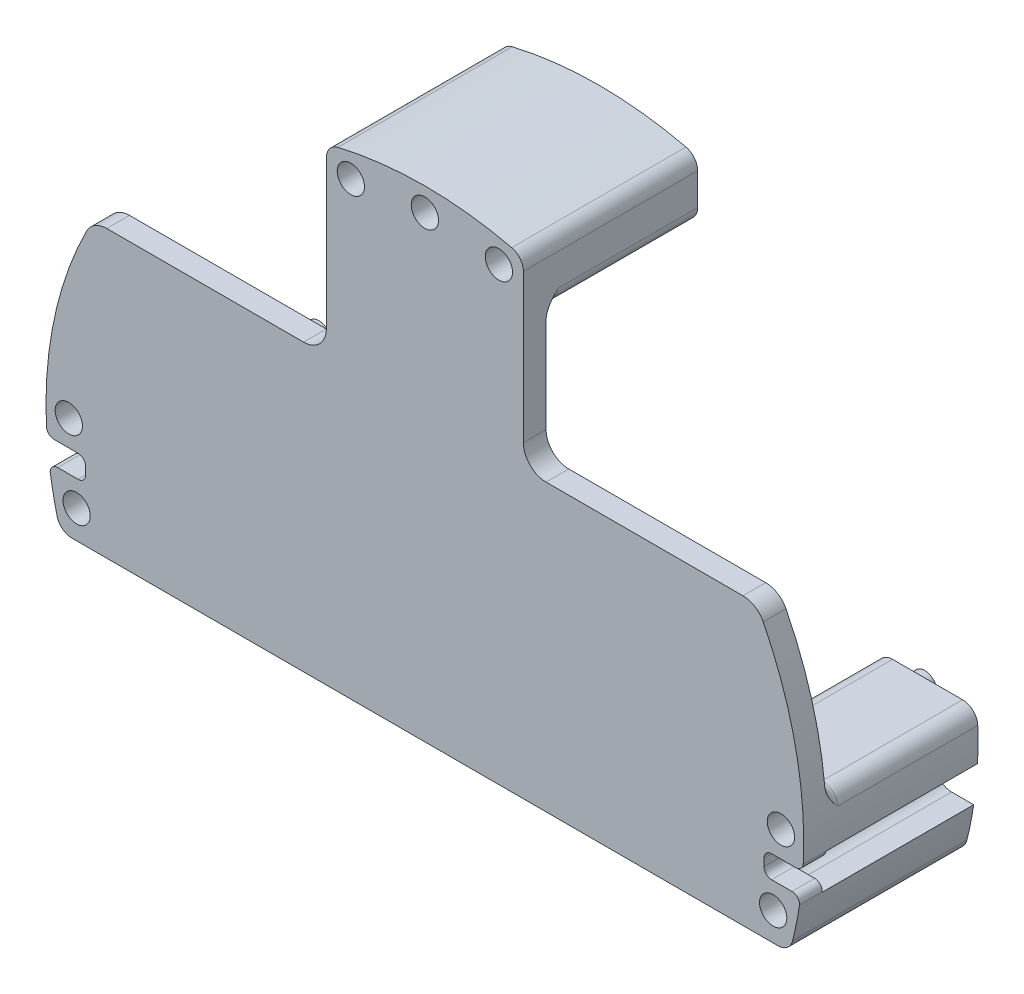
SolidWorks part; units mm, degrees
ref_plane "Front Plane" through (0, 0, 0) normal (0, 0, 1) x (1, 0, 0)
ref_plane "Top Plane" through (0, 0, 0) normal (0, 1, 0) x (1, 0, 0)
ref_plane "Right Plane" through (0, 0, 0) normal (1, 0, 0) x (0, 0, -1)
sketch "Sketch1" plane through (0, 0, 0) normal (0, 0, 1) x (1, 0, 0)
  circle A0 centre (0, 0) radius 50
  dimension "D1" = 100
extrude "Boss-Extrude1" add sketch "Sketch1" along normal blind 3
sketch "Sketch2" plane through (0, 0, 0) normal (0, 0, -1) x (-1, 0, 0)
  line L0 (14, 46.4247) -> (14, 38.9389) construction
  line L1 (-14, 38.9389) -> (-14, 46.4247) construction
  line L2 (14, 46.4247) -> (14, 38.9389) construction
  line L3 (-14, 38.9389) -> (-14, 46.4247) construction
  line L4 (20.4188, -14.0511) -> (-46.4758, -14.0511) construction
  line L5 (-42.0264, 25.1389) -> (-38.74, 25.1389) construction
  line L6 (20.4188, -14.0511) -> (-46.4758, -14.0511) construction
  line L7 (-42.0264, 25.1389) -> (-38.74, 25.1389) construction
  line L8 (38.74, 25.1389) -> (42.0265, 25.1389) construction
  line L9 (38.74, 25.1389) -> (42.0265, 25.1389) construction
  line L10 (-48.4426, -6.4208) -> (-45.7608, -6.4208) construction
  line L11 (-44.7608, -5.4208) -> (-44.7608, -4.4511) construction
  line L12 (-45.7608, -3.4511) -> (-48.9412, -3.4511) construction
  line L13 (-48.4426, -6.4208) -> (-45.7608, -6.4208)
  line L14 (-44.7608, -5.4208) -> (-44.7608, -4.4511)
  line L15 (-45.7608, -3.4511) -> (-48.9412, -3.4511)
  line L16 (45.7608, -6.4209) -> (48.4426, -6.4209) construction
  line L17 (44.7608, -4.4511) -> (44.7608, -5.4209) construction
  line L18 (48.9412, -3.4511) -> (45.7608, -3.4511) construction
  line L19 (45.7608, -6.4209) -> (48.4426, -6.4209)
  line L20 (44.7608, -4.4511) -> (44.7608, -5.4209)
  line L21 (48.9412, -3.4511) -> (45.7608, -3.4511)
  line L22 (-0.427, 43.2631) -> (13.0731, 43.2631) construction
  line L23 (-0.427, 43.2631) -> (13.0731, 43.2631) construction
  line L24 (-40.3963, 19.635) -> (-38.66, 21.3713) construction
  line L25 (-40.3963, 19.635) -> (-38.66, 21.3713) construction
  line L26 (-42.2208, 13.254) -> (-42.2208, -1.623) construction
  line L27 (-42.2208, 13.254) -> (-42.2208, -1.623) construction
  line L28 (-42.2209, -12.873) -> (-42.2209, 0.627) construction
  line L29 (-42.2209, -12.873) -> (-42.2209, 0.627) construction
  line L30 (38.279, 20.9903) -> (40.0153, 19.254) construction
  line L31 (42.3521, 0.627) -> (42.3521, -12.873) construction
  line L32 (42.3521, -1.623) -> (42.3521, 13.254) construction
  line L33 (38.279, 20.9903) -> (40.0153, 19.254) construction
  line L34 (42.3521, 0.627) -> (42.3521, -12.873) construction
  line L35 (42.3521, -1.623) -> (42.3521, 13.254) construction
  circle A0 centre (45.9632, -9.8209) radius 1.8 construction
  circle A1 centre (46.9901, -0.0511) radius 1.8 construction
  circle A2 centre (45.9632, 9.7188) radius 1.8 construction
  circle A3 centre (9.7699, 45.9121) radius 1.8 construction
  circle A4 centre (0, 46.939) radius 1.8 construction
  circle A5 centre (-9.7699, 45.9121) radius 1.8 construction
  circle A6 centre (-45.9632, -9.8209) radius 1.8 construction
  circle A7 centre (-46.9901, -0.0511) radius 1.8 construction
  circle A8 centre (-45.9632, 9.7188) radius 1.8 construction
  circle A9 centre (45.9632, -9.8209) radius 1.8
  circle A10 centre (46.9901, -0.0511) radius 1.8
  circle A11 centre (45.9632, 9.7188) radius 1.8
  circle A12 centre (9.7699, 45.9121) radius 1.8
  circle A13 centre (0, 46.939) radius 1.8
  circle A14 centre (-9.7699, 45.9121) radius 1.8
  circle A15 centre (-45.9632, -9.8209) radius 1.8
  circle A16 centre (-46.9901, -0.0511) radius 1.8
  circle A17 centre (-45.9632, 9.7188) radius 1.8
  arc A18 (-49.94, -2.5) -> (-48.9412, -3.4511) centre (-48.9412, -2.4511) ccw construction
  arc A19 (-48.4426, -6.4208) -> (-49.4312, -7.5712) centre (-48.4426, -7.4208) ccw construction
  arc A20 (-45.7608, -6.4208) -> (-44.7608, -5.4208) centre (-45.7608, -5.4208) ccw construction
  arc A21 (-44.7608, -4.4511) -> (-45.7608, -3.4511) centre (-45.7608, -4.4511) ccw construction
  arc A22 (-49.94, -2.5) -> (-48.9412, -3.4511) centre (-48.9412, -2.4511) ccw
  arc A23 (-48.4426, -6.4208) -> (-49.4312, -7.5712) centre (-48.4426, -7.4208) ccw
  arc A24 (-45.7608, -6.4208) -> (-44.7608, -5.4208) centre (-45.7608, -5.4208) ccw
  arc A25 (-44.7608, -4.4511) -> (-45.7608, -3.4511) centre (-45.7608, -4.4511) ccw
  arc A26 (44.7608, -5.4209) -> (45.7608, -6.4209) centre (45.7608, -5.4209) ccw construction
  arc A27 (45.7608, -3.4511) -> (44.7608, -4.4511) centre (45.7608, -4.4511) ccw construction
  arc A28 (48.9412, -3.4511) -> (49.94, -2.5001) centre (48.9412, -2.4511) ccw construction
  arc A29 (49.4312, -7.5713) -> (48.4426, -6.4209) centre (48.4426, -7.4209) ccw construction
  arc A30 (44.7608, -5.4209) -> (45.7608, -6.4209) centre (45.7608, -5.4209) ccw
  arc A31 (45.7608, -3.4511) -> (44.7608, -4.4511) centre (45.7608, -4.4511) ccw
  arc A32 (48.9412, -3.4511) -> (49.94, -2.5001) centre (48.9412, -2.4511) ccw
  arc A33 (49.4312, -7.5713) -> (48.4426, -6.4209) centre (48.4426, -7.4209) ccw
  arc A34 (-49.94, -2.5) -> (-49.4312, -7.5712) centre (-44.6835, -4.5338) ccw
  arc A35 (49.94, -2.5001) -> (49.4312, -7.5713) centre (49.0397, -4.9709) cw
  circle A36 centre (38.3005, -27.2416) radius 1.8 construction
  circle A37 centre (44.1819, 15.9698) radius 1.2 construction
  circle A38 centre (41.555, 21.9154) radius 1.2 construction
  circle A39 centre (32.7399, 26.939) radius 1.8 construction
  circle A40 centre (4.9119, 46.6815) radius 1.2 construction
  circle A41 centre (-4.9119, 46.6815) radius 1.2 construction
  circle A42 centre (-32.7399, 26.939) radius 1.8 construction
  circle A43 centre (-41.555, 21.9154) radius 1.2 construction
  circle A44 centre (-44.1819, 15.9698) radius 1.2 construction
  circle A45 centre (38.3005, -27.2416) radius 1.8 construction
  circle A46 centre (44.1819, 15.9698) radius 1.2 construction
  circle A47 centre (41.555, 21.9154) radius 1.2 construction
  circle A48 centre (32.7399, 26.939) radius 1.8 construction
  circle A49 centre (4.9119, 46.6815) radius 1.2 construction
  circle A50 centre (-4.9119, 46.6815) radius 1.2 construction
  circle A51 centre (-32.7399, 26.939) radius 1.8 construction
  circle A52 centre (-41.555, 21.9154) radius 1.2 construction
  circle A53 centre (-44.1819, 15.9698) radius 1.2 construction
extrude "Cut-Extrude1" cut sketch "Sketch2" against normal through all
sketch "Sketch3" plane through (0, 0, 0) normal (0, 0, -1) x (-1, 0, 0)
  line L0 (-48.1287, -13.5511) -> (-42.7209, -13.5511)
  line L1 (-42.7209, -13.5511) -> (-42.7209, 14.254)
  line L2 (-42.7209, 14.254) -> (-47.9252, 14.254) construction
  line L9 (20.4188, -14.0511) -> (-46.4758, -14.0511) construction
  line L10 (-42.2209, -12.873) -> (-42.2209, 0.627) construction
  line L11 (0, 0) -> (0, 49.9989) construction
  line L12 (0, 43.5131) -> (-13, 43.5131)
  line L13 (-13, 43.5131) -> (-13, 48.2804)
  line L14 (-14, 38.9389) -> (-14, 46.4247) construction
  line L15 (-0.427, 43.2631) -> (13.0731, 43.2631) construction
  line L16 (0, 43.5131) -> (13, 43.5131)
  line L17 (13, 43.5131) -> (13, 48.2804)
  line L24 (-42.7209, 14.254) -> (-40.8963, 19.635)
  line L25 (-40.8963, 19.635) -> (-36.3924, 24.1389)
  line L26 (-36.3924, 24.1389) -> (-43.7871, 24.1389)
  line L27 (-40.3963, 19.635) -> (-40.8963, 19.635) construction
  line L28 (-40.3963, 19.635) -> (-40.3963, 14.254) construction
  line L29 (-40.3963, 14.254) -> (-42.7209, 14.254) construction
  line L30 (-40.3963, 19.635) -> (-38.66, 21.3713) construction
  line L31 (-42.0264, 25.1389) -> (-38.74, 25.1389) construction
  line L32 (-49.4311, -7.5208) -> (-44.5108, -7.5208)
  line L33 (-48.4426, -6.4208) -> (-45.7608, -6.4208) construction
  line L34 (40.3963, 14.254) -> (42.7209, 14.254) construction
  line L35 (40.3963, 19.635) -> (40.3963, 14.254) construction
  line L44 (-49.9338, -2.5725) -> (-44.5108, -2.5725)
  line L45 (-44.5108, -2.5725) -> (-44.5108, -7.5208)
  line L50 (-44.7608, -5.4208) -> (-44.7608, -4.4511) construction
  line L69 (40.3963, 19.635) -> (40.8963, 19.635) construction
  line L70 (42.7209, 14.254) -> (47.9252, 14.254) construction
  line L71 (44.5108, -2.5725) -> (44.5108, -7.5208)
  line L72 (49.9338, -2.5725) -> (44.5108, -2.5725)
  line L73 (49.4311, -7.5208) -> (44.5108, -7.5208)
  line L74 (36.3924, 24.1389) -> (43.7871, 24.1389)
  line L75 (40.8963, 19.635) -> (36.3924, 24.1389)
  line L76 (42.7209, 14.254) -> (40.8963, 19.635)
  line L77 (42.7209, -13.5511) -> (42.7209, 14.254)
  line L78 (48.1287, -13.5511) -> (42.7209, -13.5511)
  arc A0 (-49.4423, -7.4473) -> (49.4423, -7.4473) centre (0, 0) ccw construction
  arc A1 (49.9338, -2.5729) -> (-49.9338, -2.5725) centre (0, 0) ccw construction
  arc A2 (-47.9252, 14.254) -> (-49.9338, -2.5725) centre (0, 0) ccw
  arc A12 (-13, 48.2804) -> (13, 48.2804) centre (0, 0) cw
  circle A19 centre (-45.9632, 9.7188) radius 1.8 construction
  circle A20 centre (-46.9901, -0.0511) radius 1.8 construction
  circle A21 centre (-45.9632, -9.8209) radius 1.8 construction
  circle A22 centre (-9.7699, 45.9121) radius 1.8 construction
  circle A26 centre (9.7699, 45.9121) radius 1.8 construction
  circle A27 centre (0, 46.939) radius 1.8 construction
  circle A31 centre (9.7699, 45.9121) radius 1.8
  circle A32 centre (0, 46.939) radius 1.8
  circle A33 centre (-9.7699, 45.9121) radius 1.8
  circle A34 centre (-45.9632, -9.8209) radius 1.8
  circle A35 centre (-46.9901, -0.0511) radius 1.8
  circle A36 centre (-45.9632, 9.7188) radius 1.8 construction
  arc A37 (-43.7871, 24.1389) -> (-47.9252, 14.254) centre (0, 0) ccw
  arc A58 (-48.1287, -13.5511) -> (-49.4311, -7.5208) centre (0, 0) cw
  circle A59 centre (45.9632, 9.7188) radius 1.8 construction
  arc A60 (48.1287, -13.5511) -> (49.4311, -7.5208) centre (0, 0) ccw
  arc A61 (43.7871, 24.1389) -> (47.9252, 14.254) centre (0, 0) cw
  circle A62 centre (46.9901, -0.0511) radius 1.8
  circle A63 centre (45.9632, -9.8209) radius 1.8
  arc A64 (47.9252, 14.254) -> (49.9338, -2.5725) centre (0, 0) cw
  dimension "D1" = 0.5
  dimension "D2" = 0.5
  dimension "D3" = 1
  dimension "D4" = 1
  dimension "D5" = 0.25
  dimension "D6" = 0.5
  dimension "D7" = 1
  dimension "D8" = 0.25
  dimension "D9" = 1.1
extrude "Boss-Extrude2" add sketch "Sketch3" along normal blind 20
sketch "Sketch10" plane through (0, 0, -20) normal (0, 0, -1) x (-1, 0, 0)
  line L3 (0, 0) -> (0, 43.5131) construction
  line L8 (-42.7209, -13.5511) -> (-42.7209, 14.254) construction
  line L10 (-42.7209, -13.5511) -> (-42.7209, 3.7489)
  line L16 (-36.7209, 3.7489) -> (-36.7209, -13.5511)
  line L17 (-36.7209, -13.5511) -> (-42.7209, -13.5511)
  line L18 (-13, 43.5131) -> (13, 43.5131) construction
  line L19 (42.7209, 3.7489) -> (36.7209, 3.7489)
  line L26 (-42.7209, 3.7489) -> (-36.7209, 3.7489)
  line L27 (-42.7209, 3.7489) -> (-49.8593, 3.7489) construction
  line L28 (-46.9901, 1.7489) -> (-42.7209, 1.7489) construction
  line L29 (42.7209, -13.5511) -> (42.7209, 3.7489)
  line L30 (36.7209, -13.5511) -> (42.7209, -13.5511)
  line L31 (36.7209, 3.7489) -> (36.7209, -13.5511)
  arc A0 (-43.7871, 24.1389) -> (-49.9338, -2.5725) centre (0, 0) ccw construction
  circle A1 centre (-46.9901, -0.0511) radius 1.8 construction
  dimension "D1" = 6
  dimension "D2" = 2
extrude "Boss-Extrude6" add sketch "Sketch10" against normal up to surface (20 mm away) up to face at (0, 16.4713, 0)
sketch "Sketch4" plane through (0, 0, -20) normal (0, 0, -1) x (-1, 0, 0)
  circle A0 centre (41.555, 21.9154) radius 1.2 construction
  circle A1 centre (44.1819, 15.9698) radius 1.2 construction
  circle A2 centre (-44.1819, 15.9698) radius 1.2 construction
  circle A3 centre (-41.555, 21.9154) radius 1.2 construction
  circle A4 centre (41.555, 21.9154) radius 1.2 construction
  circle A5 centre (44.1819, 15.9698) radius 1.2 construction
  circle A6 centre (-44.1819, 15.9698) radius 1.2 construction
  circle A7 centre (-41.555, 21.9154) radius 1.2 construction
  circle A8 centre (-41.555, 21.9154) radius 1.1
  circle A9 centre (-44.1819, 15.9698) radius 1.1
  circle A10 centre (41.555, 21.9154) radius 1.1
  circle A11 centre (44.1819, 15.9698) radius 1.1
  circle A12 centre (45.9632, 9.7188) radius 1.8 construction
  circle A13 centre (-45.9632, 9.7188) radius 1.8 construction
  circle A14 centre (45.9632, 9.7188) radius 1.8 construction
  circle A15 centre (-45.9632, 9.7188) radius 1.8 construction
  circle A16 centre (-45.9632, 9.7188) radius 1.6
  circle A17 centre (45.9632, 9.7188) radius 1.6
  circle A18 centre (4.9119, 46.6815) radius 1.2 construction
  circle A19 centre (-4.9119, 46.6815) radius 1.2 construction
  circle A20 centre (4.9119, 46.6815) radius 1.2 construction
  circle A21 centre (-4.9119, 46.6815) radius 1.2 construction
  circle A22 centre (-4.9119, 46.6815) radius 1.1
  circle A23 centre (4.9119, 46.6815) radius 1.1
  dimension "D1" = 2.2
  dimension "D2" = 3.2
extrude "Boss-Extrude3" add sketch "Sketch4" along normal blind 1.6
sketch "Sketch14" plane through (0, 0, 0) normal (0, 0, -1) x (-1, 0, 0)
  line L0 (13, 43.5131) -> (13, 48.2804) construction
  line L1 (-13, 43.5131) -> (13, 43.5131)
  line L2 (-13, 43.5131) -> (-13, 40.5131)
  line L3 (-13, 40.5131) -> (13, 40.5131)
  line L4 (13, 43.5131) -> (13, 40.5131)
  dimension "D1" = 3
extrude "Boss-Extrude8" add sketch "Sketch14" along normal up to surface (20 mm away) up to face at (-3.8119, 46.6815, -20)
sketch "Sketch11" plane through (0, 0, -20) normal (0, 0, -1) x (-1, 0, 0)
  line L0 (-45.9632, 9.7188) -> (45.9632, 9.7188) construction
  line L1 (45.9632, 9.7188) -> (44.1819, 15.9698) construction
  line L2 (44.1819, 15.9698) -> (-44.1822, 15.9698) construction
  line L3 (-44.1822, 15.9698) -> (-41.555, 21.9154) construction
  line L4 (-41.555, 21.9154) -> (41.555, 21.9154) construction
  line L5 (-45.9632, -9.8209) -> (45.9632, -9.8209) construction
  line L6 (45.9632, -9.8209) -> (-46.9798, 0) construction
  line L7 (-46.9798, 0) -> (46.9798, 0) construction
  circle A0 centre (0, 0) radius 39.9798 construction
  circle A1 centre (0, 0) radius 46.9798 construction
  circle A11 centre (-39.9798, 0) radius 1.6
  circle A12 centre (-38.7548, -9.8209) radius 1.6
  circle A13 centre (38.7548, -9.8209) radius 1.6
  circle A14 centre (39.9798, 0) radius 1.6
  circle A15 centre (-45.9632, 9.7188) radius 1.6 construction
  dimension "D1" = 7
extrude "Boss-Extrude7" add sketch "Sketch11" along normal blind 3
sketch "Sketch15" plane through (0, 0, -20) normal (0, 0, -1) x (-1, 0, 0)
  line L0 (-13, 41.7631) -> (13, 41.7631) construction
  line L1 (-13, 48.2804) -> (-13, 40.5131) construction
  line L2 (13, 40.5131) -> (13, 48.2804) construction
  line L3 (13, 41.7631) -> (4.9119, 46.6815) construction
  line L4 (4.9119, 46.6815) -> (-4.9119, 46.6815) construction
  line L5 (-4.9119, 46.6815) -> (-4.9119, 40.5131) construction
  line L6 (-13, 40.5131) -> (13, 40.5131) construction
  line L7 (-4.9119, 40.5131) -> (4.9119, 46.6815) construction
  line L8 (4.9119, 46.6815) -> (4.9119, 40.5131) construction
  line L9 (13, 40.5131) -> (-13, 40.5131) construction
  circle A0 centre (-4.9119, 41.7631) radius 1.1
  circle A1 centre (4.9119, 41.7631) radius 1.1
  circle A2 centre (-4.9119, 46.6815) radius 1.1 construction
  circle A3 centre (4.9119, 46.6815) radius 1.1 construction
  dimension "D1" = 1.25
extrude "Boss-Extrude9" add sketch "Sketch15" along normal up to surface (3 mm away) up to face at (38.3798, 0, -23)
sketch "Sketch13" plane through (0, 0, -21.6) normal (0, 0, -1) x (-1, 0, 0)
  circle A0 centre (45.9632, 9.7188) radius 1.6 construction
  circle A1 centre (44.1819, 15.9698) radius 1.1 construction
  circle A2 centre (41.555, 21.9154) radius 1.1 construction
  circle A3 centre (-41.555, 21.9154) radius 1.1 construction
  circle A4 centre (-44.1819, 15.9698) radius 1.1 construction
  circle A5 centre (-45.9632, 9.7188) radius 1.6 construction
  circle A6 centre (45.9632, 9.7188) radius 1.6
  circle A7 centre (44.1819, 15.9698) radius 1.1
  circle A8 centre (41.555, 21.9154) radius 1.1
  circle A9 centre (-41.555, 21.9154) radius 1.1
  circle A10 centre (-44.1819, 15.9698) radius 1.1
  circle A11 centre (-45.9632, 9.7188) radius 1.6
  circle A12 centre (4.9119, 46.6815) radius 1.1 construction
  circle A13 centre (-4.9119, 46.6815) radius 1.1 construction
  circle A14 centre (4.9119, 46.6815) radius 1.1
  circle A15 centre (-4.9119, 46.6815) radius 1.1
extrude "Cut-Extrude6" cut sketch "Sketch13" against normal up to surface (1.6 mm away) up to face at (40.3548, -9.8209, -20)
sketch "Sketch16" plane through (0, 0, -20) normal (0, 0, -1) x (-1, 0, 0)
  line L0 (-42.7209, 3.7489) -> (-49.8593, 3.7489)
  line L1 (-36.3924, 24.1389) -> (-43.7871, 24.1389) construction
  line L2 (-40.8963, 19.635) -> (-36.3924, 24.1389) construction
  line L3 (-42.7209, 14.254) -> (-40.8963, 19.635) construction
  line L4 (-42.7209, 3.7489) -> (-42.7209, 14.254) construction
  line L5 (-36.3924, 24.1389) -> (-43.7871, 24.1389)
  line L6 (-40.8963, 19.635) -> (-36.3924, 24.1389)
  line L7 (-42.7209, 14.254) -> (-40.8963, 19.635)
  line L8 (-42.7209, 3.7489) -> (-42.7209, 14.254)
  line L9 (0, 0) -> (0, 40.5131) construction
  line L10 (-13, 40.5131) -> (13, 40.5131) construction
  line L11 (40.8963, 19.635) -> (36.3924, 24.1389)
  line L12 (42.7209, 14.254) -> (40.8963, 19.635)
  line L13 (42.7209, 3.7489) -> (42.7209, 14.254)
  line L14 (42.7209, 3.7489) -> (49.8593, 3.7489)
  line L15 (36.3924, 24.1389) -> (43.7871, 24.1389)
  arc A0 (-43.7871, 24.1389) -> (-49.9338, -2.5725) centre (0, 0) ccw construction
  arc A1 (-43.7871, 24.1389) -> (-49.8593, 3.7489) centre (0, 0) ccw
  arc A2 (43.7871, 24.1389) -> (49.8593, 3.7489) centre (0, 0) cw
extrude "Cut-Extrude7" cut sketch "Sketch16" against normal up to surface (20 mm away) up to face at (0, 13.6268, 0)
sketch "Sketch17" plane through (0, 0, 0) normal (0, 0, -1) x (-1, 0, 0)
  line L0 (-48.1287, -13.5511) -> (48.1287, -13.5511)
  arc A0 (-48.1287, -13.5511) -> (48.1287, -13.5511) centre (0, 0) ccw construction
  arc A1 (-48.1287, -13.5511) -> (48.1287, -13.5511) centre (0, 0) ccw
extrude "Cut-Extrude8" cut sketch "Sketch17" against normal through all both and the other way through all
fillet "Fillet1" radius 2 16 edges at (-36.7209, 3.7489, -10) (-36.7209, -13.5511, -10) (36.7209, -13.5511, -10) (36.7209, 3.7489, -10) (-13, 48.2804, -10) (44.5108, -7.5208, -10) (44.5108, -2.5725, -10) (-44.5108, -7.5208, -10) (-44.5108, -2.5725, -10) (-49.8593, 3.7489, -10) (-48.1287, -13.5511, -8.5) (-13, 40.5131, -10) (13, 48.2804, -10) (13, 40.5131, -10) (49.8593, 3.7489, -10) (48.1287, -13.5511, -8.5)
sketch "Sketch18" plane through (0, 0, 0) normal (0, 0, -1) x (-1, 0, 0)
  line L0 (-40.8905, 27.1389) -> (-33, 27.1389) construction
  line L1 (-13, 29.1389) -> (-13, 46.7226) construction
  line L2 (-40.8905, 27.1389) -> (-15, 27.1389)
  line L3 (-13, 29.1389) -> (-13, 46.7226)
  line L4 (0, 0) -> (0, 47.7712) construction
  line L5 (13, 29.1389) -> (13, 46.7226)
  line L6 (40.8905, 27.1389) -> (15, 27.1389)
  arc A0 (-40.8905, 27.1389) -> (-42.5943, 26.1864) centre (-40.8905, 25.1389) ccw construction
  arc A2 (-11.4583, 48.6694) -> (-13, 46.7226) centre (-11, 46.7226) ccw construction
  arc A3 (-40.8905, 27.1389) -> (-42.5943, 26.1864) centre (-40.8905, 25.1389) ccw
  arc A4 (-15, 27.1389) -> (-13, 29.1389) centre (-15, 29.1389) ccw
  arc A5 (-11.4583, 48.6694) -> (-13, 46.7226) centre (-11, 46.7226) ccw
  arc A6 (-11.4583, 48.6694) -> (-42.5943, 26.1864) centre (0, 0) ccw
  arc A7 (11.4583, 48.6694) -> (13, 46.7226) centre (11, 46.7226) cw
  arc A8 (15, 27.1389) -> (13, 29.1389) centre (15, 29.1389) cw
  arc A9 (40.8905, 27.1389) -> (42.5943, 26.1864) centre (40.8905, 25.1389) cw
  arc A10 (11.4583, 48.6694) -> (42.5943, 26.1864) centre (0, 0) cw
  dimension "D1" = 2
extrude "Cut-Extrude9" cut sketch "Sketch18" against normal through all both
fillet "Fillet2" radius 1.5 13 edges at (12.4142, 41.0989, 0) (-12.4142, 41.0989, 0) (-49.3563, 3.1887, 0) (-43.3445, 3.7489, 0) (-37.3067, 3.1632, 0) (-37.3067, -12.9653, 0) (37.3067, -12.9653, 0) (49.3563, 3.1887, 0) (43.3445, 3.7489, 0) (37.3067, 3.1632, 0) (0, 40.5131, 0) (-36.7209, -4.9011, 0) (36.7209, -4.9011, 0)
sketch "Sketch9" plane through (0, 0, 3) normal (0, 0, 1) x (1, 0, 0)
  circle A0 centre (45.9632, 9.7188) radius 1.8 construction
  circle A2 centre (45.9632, 9.7188) radius 1.8
  circle A4 centre (-45.9632, 9.7188) radius 1.8 construction
  circle A5 centre (-45.9632, 9.7188) radius 1.8
extrude "Boss-Extrude5" add sketch "Sketch9" against normal up to surface (3 mm away) up to face at (0, 15.0845, 0)
sketch "Sketch24" plane through (0, 0, 0) normal (0, 0, -1) x (-1, 0, 0)
  line L0 (0, 40.5131) -> (0, 0) construction
  line L1 (-13, 29.1389) -> (-53, 29.1389)
  line L2 (-13, 29.1389) -> (-13, 24.1389)
  line L3 (-13, 24.1389) -> (-53, 24.1389)
  line L4 (-53, 29.1389) -> (-53, 24.1389)
  line L5 (11, 40.5131) -> (-11, 40.5131) construction
  line L6 (13, 24.1389) -> (53, 24.1389)
  line L7 (53, 29.1389) -> (53, 24.1389)
  line L8 (13, 29.1389) -> (53, 29.1389)
  line L9 (13, 29.1389) -> (13, 24.1389)
  line L10 (-13, 29.1389) -> (-13, 39.6408) construction
  arc A0 (-15, 27.1389) -> (-13, 29.1389) centre (-15, 29.1389) ccw construction
  dimension "D1" = 40
  dimension "D2" = 5
extrude "Cut-Extrude10" cut sketch "Sketch24" against normal through all
fillet "Fillet4" radius 3 4 edges at (-13, 24.1389, 1.5) (13, 24.1389, 1.5) (-43.7871, 24.1389, 1.5) (43.7871, 24.1389, 1.5)
